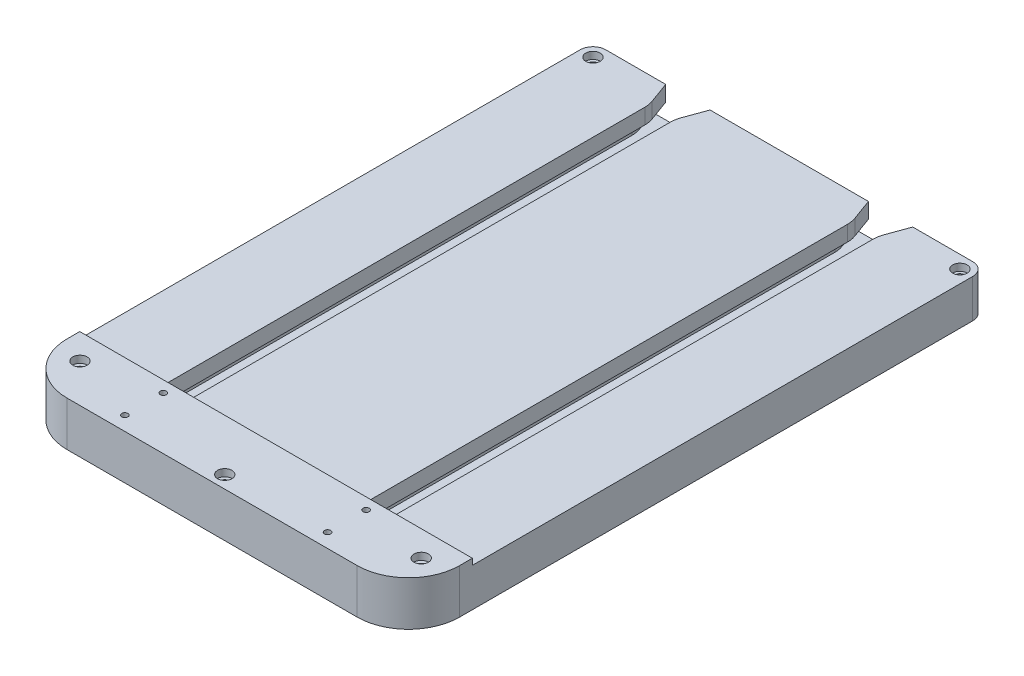
SolidWorks part; units mm, degrees
ref_plane "Front Plane" through (0, 0, 0) normal (0, 0, 1) x (1, 0, 0)
ref_plane "Top Plane" through (0, 0, 0) normal (0, 1, 0) x (1, 0, 0)
ref_plane "Right Plane" through (0, 0, 0) normal (1, 0, 0) x (0, 0, -1)
sketch "Sketch1" plane through (0, 0, 0) normal (0, 0, 1) x (1, 0, 0)
  line L0 (8.5758, -1.4682) -> (8.5758, -16.2855) construction
  line L1 (-88.5792, 2.7645) -> (-47.9392, 2.7645)
  line L2 (-88.5792, 2.7645) -> (-88.5792, -16.2855)
  line L3 (-88.5792, -16.2855) -> (105.7308, -16.2855)
  line L4 (105.7308, 2.7645) -> (105.7308, -16.2855)
  line L7 (-35.2392, 2.7645) -> (-35.2392, -4.8555)
  line L9 (-47.9392, 2.7645) -> (-47.9392, -4.8555)
  line L10 (-54.2892, -4.8555) -> (-47.9392, -4.8555)
  line L11 (-54.2892, -4.8555) -> (-54.2892, -12.4755)
  line L12 (-54.2892, -12.4755) -> (-28.8892, -12.4755)
  line L13 (-28.8892, -4.8555) -> (-28.8892, -12.4755)
  line L14 (65.0908, 2.7645) -> (65.0908, -4.8555)
  line L16 (52.3908, 2.7645) -> (52.3908, -4.8555)
  line L17 (71.4408, -12.4755) -> (46.0408, -12.4755)
  line L18 (46.0408, -4.8555) -> (46.0408, -12.4755)
  line L19 (71.4408, -4.8555) -> (65.0908, -4.8555)
  line L20 (71.4408, -4.8555) -> (71.4408, -12.4755)
  line L21 (-35.2392, -4.8555) -> (-28.8892, -4.8555)
  line L22 (-35.2392, 2.7645) -> (5.4008, 2.7645)
  line L23 (52.3908, -4.8555) -> (46.0408, -4.8555)
  line L24 (65.0908, 2.7645) -> (105.7308, 2.7645)
  line L25 (11.7508, 2.7645) -> (52.3908, 2.7645)
  line L27 (5.4008, 2.7645) -> (5.4008, 28.1645)
  line L28 (5.4008, 28.1645) -> (11.7508, 28.1645)
  line L29 (11.7508, 2.7645) -> (11.7508, 28.1645)
  dimension "D1" = 19.05
  dimension "D2" = 7.62
  dimension "D3" = 25.4
  dimension "D4" = 7.62
  dimension "D5" = 12.7
  dimension "D6" = 43.815
  dimension "D7" = 40.64
  dimension "D8" = 25.4
  dimension "D9" = 6.35
extrude "Boss-Extrude1" add sketch "Sketch1" along normal blind 254
sketch "Sketch2" plane through (0, 0, 254) normal (0, 0, 1) x (1, 0, 0)
  line L0 (105.7308, -16.2855) -> (105.7308, 2.7645) construction
  line L1 (-88.5792, -16.2855) -> (105.7308, -16.2855)
  line L2 (-88.5792, -16.2855) -> (-88.5792, 28.1645)
  line L3 (-88.5792, 28.1645) -> (105.7308, 28.1645)
  line L4 (105.7308, -16.2855) -> (105.7308, 28.1645)
  line L5 (11.7508, 28.1645) -> (5.4008, 28.1645) construction
  line L6 (105.7308, -16.2855) -> (105.7308, 2.7645)
  line L7 (11.7508, 28.1645) -> (5.4008, 28.1645)
  line L8 (5.4008, 2.7645) -> (-35.2392, 2.7645) construction
  line L9 (-35.2392, 2.7645) -> (-35.2392, -4.8555) construction
  line L10 (-47.9392, -4.8555) -> (-47.9392, 2.7645) construction
  line L11 (-47.9392, 2.7645) -> (-88.5792, 2.7645) construction
  line L12 (5.4008, 2.7645) -> (-35.2392, 2.7645)
  line L13 (-35.2392, 2.7645) -> (-35.2392, -4.8555)
  line L14 (-47.9392, -4.8555) -> (-47.9392, 2.7645)
  line L15 (-47.9392, 2.7645) -> (-88.5792, 2.7645)
  line L16 (8.5758, 28.1645) -> (8.5758, -16.2855) construction
  line L17 (-47.9392, 2.7645) -> (-35.2392, 2.7645)
  line L22 (-41.5892, 2.7645) -> (-41.5892, 5.8125)
  line L23 (-59.3692, 22.8305) -> (-23.8092, 22.8305)
  line L24 (-59.3692, 22.8305) -> (-59.3692, 5.8125)
  line L25 (-59.3692, 5.8125) -> (-23.8092, 5.8125)
  line L26 (-23.8092, 22.8305) -> (-23.8092, 5.8125)
  line L27 (76.5208, 5.8125) -> (40.9608, 5.8125)
  line L28 (40.9608, 22.8305) -> (40.9608, 5.8125)
  line L29 (76.5208, 22.8305) -> (40.9608, 22.8305)
  line L30 (76.5208, 22.8305) -> (76.5208, 5.8125)
  dimension "D1" = 17.018
  dimension "D2" = 35.56
  dimension "D3" = 3.048
  dimension "D4" = 90
extrude "Boss-Extrude2" add sketch "Sketch2" along normal blind 6.35
sketch "Sketch3" plane through (0, 0, 260.35) normal (0, 0, 1) x (1, 0, 0)
  line L0 (105.7308, -16.2855) -> (105.7308, 28.1645) construction
  line L1 (-88.5792, -16.2855) -> (105.7308, -16.2855)
  line L2 (-88.5792, -16.2855) -> (-88.5792, 5.8125)
  line L3 (-88.5792, 5.8125) -> (105.7308, 5.8125)
  line L4 (105.7308, -16.2855) -> (105.7308, 5.8125)
  line L5 (76.5208, 5.8125) -> (40.9608, 5.8125) construction
  line L6 (105.7308, -16.2855) -> (105.7308, 28.1645)
  line L7 (76.5208, 5.8125) -> (40.9608, 5.8125)
  line M8 (-88.5792, 28.1645) -> (-88.5792, -16.2855)
  line M9 (-88.5792, -16.2855) -> (105.7308, -16.2855)
  line M10 (105.7308, -16.2855) -> (105.7308, 28.1645)
  line M13 (76.5208, 5.8125) -> (40.9608, 5.8125)
  line M15 (-23.8092, 5.8125) -> (-59.3692, 5.8125)
extrude "Boss-Extrude3" add sketch "Sketch3" along normal blind 44.45 contours L3 M8 M9 M10 M13 M15
ref_plane "Plane1" through (-54.2892, -12.4755, 254) normal (-1, 0, 0) x (0, 0, 1)
sketch "Sketch5" plane through (0, 5.8125, 0) normal (0, 1, 0) x (1, 0, 0)
  line L0 (-41.5892, -254) -> (-41.5892, -329.45) construction
  line L1 (-59.3692, -254) -> (-23.8092, -254) construction
  line L2 (8.5758, -260.35) -> (8.5758, -328.2895) construction
  line L3 (-23.8092, -260.35) -> (40.9608, -260.35) construction
  circle A0 centre (-41.5892, -259.614) radius 1.524
  circle A1 centre (-41.5892, -278.664) radius 1.524
  circle A2 centre (58.7408, -259.614) radius 1.524
  circle A3 centre (58.7408, -278.664) radius 1.524
  dimension "D1" = 3.048
  dimension "D2" = 3.048
  dimension "D3" = 5.614
  dimension "D4" = 19.05
extrude "Cut-Extrude1" cut sketch "Sketch5" against normal through all and the other way through all contours A0 | A1 | A3 | A2
fillet "Fillet1" radius 3.175 3 edges at (8.5758, 28.1645, 0) (5.4008, 28.1645, 127) (11.7508, 28.1645, 127)
fillet "Fillet2" radius 3.175 8 edges at (8.5758, 28.1645, 260.35) (82.9031, 28.1645, 260.35) (58.7408, 28.1645, 258.09) (-41.5892, 28.1645, 258.09) (6.3308, 27.2346, 254) (-40.0017, 28.1645, 254) (-65.7514, 28.1645, 260.35) (-88.5792, 28.1645, 257.175)
hole_wizard "CBORE for #6 Socket Head Cap Screw1" positions "Sketch6" profile "Sketch7" counterbore size "#6" standard "ANSI Inch" end condition through all
sketch "Sketch6" plane through (0, 2.7645, 0) normal (0, 1, 0) x (1, 0, 0)
  line L0 (105.7308, 0) -> (65.0908, 0) construction
  line L1 (105.7308, -254) -> (105.7308, 0) construction
  line L2 (-88.5792, -254) -> (-88.5792, 0) construction
  line L3 (-47.9392, 0) -> (-88.5792, 0) construction
  point P0 (99.3808, -6.35)
  point P2 (-82.2292, -6.35)
  dimension "D1" = 6.35
  dimension "D2" = 6.35
  dimension "D3" = 6.35
  dimension "D4" = 6.35
sketch "Sketch7" plane through (99.3808, 2.7645, 6.35) normal (1, 0, 0) x (0, 0, 1)
  line L0 (0, 0) -> (0, 19.05)
  line L1 (0, 19.05) -> (2.1527, 19.05)
  line L3 (2.1527, 19.05) -> (2.1526, 3.5052)
  line L4 (2.1526, 3.5052) -> (3.5725, 3.5052)
  line L5 (3.5725, 3.5052) -> (3.5725, 0)
  line L7 (3.5725, 0) -> (0, 0)
  line L11 (0, -6.35) -> (0, 107.95) construction
  dimension "Thru Hole Dia." = 4.3053
  dimension "Thru Hole Depth" = 19.05
  dimension "C'Bore Dia." = 7.145
  dimension "C'Bore Depth" = 3.5052
chamfer "Chamfer1" distance 12.7 angle 20 8 edges at (-28.8892, -8.6655, 0) (-35.2392, -1.0455, 0) (-47.9392, -1.0455, 0) (-54.2892, -8.6655, 0) (52.3908, -1.0455, 0) (46.0408, -8.6655, 0) (71.4408, -8.6655, 0) (65.0908, -1.0455, 0)
fillet "Fillet4" radius 12.7 8 edges at (65.0908, -1.0455, 12.7) (52.3908, -1.0455, 12.7) (46.0408, -8.6655, 12.7) (71.4408, -8.6655, 12.7) (-54.2892, -8.6655, 12.7) (-28.8892, -8.6655, 12.7) (-35.2392, -1.0455, 12.7) (-47.9392, -1.0455, 12.7)
fillet "Fillet6" radius 6.35 2 edges at (-88.5792, -6.7605, 0) (105.7308, -6.7605, 0)
fillet "Fillet7" radius 2.54 3 edges at (5.4008, 13.877, 0) (8.5758, 28.1645, 0) (11.7508, 13.877, 0)
sketch "Sketch8" plane through (105.7308, 0, 0) normal (1, 0, 0) x (0, 0, -1)
  line L1 (-254, 2.7645) -> (3.9998, 2.7645)
  line L2 (-254, 2.7645) -> (-254, 5.8125)
  line L3 (-234.4635, 41.9327) -> (3.9998, 41.9327)
  line L4 (3.9998, 2.7645) -> (3.9998, 41.9327)
  line L5 (-260.35, 5.8125) -> (-254, 5.8125)
  line L6 (-260.35, 5.8125) -> (-260.35, 51.3744)
  line L7 (-260.35, 51.3744) -> (-234.4635, 51.3744)
  line L8 (-234.4635, 41.9327) -> (-234.4635, 51.3744)
  dimension "D2" = 257.9998
  dimension "D3" = 45.5619
extrude "Cut-Extrude2" cut sketch "Sketch8" against normal through all
sketch "Sketch13" plane through (105.7308, 0, 0) normal (1, 0, 0) x (0, 0, -1)
  line L1 (-304.8, -16.2855) -> (-285.6568, -16.2855)
  line L2 (-304.8, -16.2855) -> (-304.8, 26.8072)
  line L3 (-304.8, 26.8072) -> (-285.6568, 26.8072)
  line L4 (-285.6568, -16.2855) -> (-285.6568, 26.8072)
  dimension "D1" = 43.0927
  dimension "D2" = 19.1432
extrude "Cut-Extrude3" cut sketch "Sketch13" against normal through all
fillet "Fillet8" radius 25.4 2 edges at (-88.5792, -5.2365, 285.6568) (105.7308, -5.2365, 285.6568)
sketch "Sketch14" plane through (0, 5.8125, 0) normal (0, 1, 0) x (1, 0, 0)
  line L0 (80.3308, -285.6568) -> (-63.1792, -285.6568) construction
  line L1 (-88.5792, -260.2568) -> (-88.5792, -254) construction
  line L2 (105.7308, -254) -> (105.7308, -6.35) construction
  circle A0 centre (93.0308, -266.6068) radius 3.175
  circle A1 centre (-75.8792, -266.6068) radius 3.175
  dimension "D1" = 6.35
  dimension "D2" = 19.05
  dimension "D3" = 12.7
  dimension "D4" = 19.05
  dimension "D5" = 12.7
hole_wizard "CBORE for #6 Socket Head Cap Screw3" positions "Sketch11" profile "Sketch12" counterbore size "#6" standard "ANSI Inch" end condition through all
sketch "Sketch11" plane through (0, 5.8125, 0) normal (0, 1, 0) x (1, 0, 0)
  line L0 (-88.5792, -260.2568) -> (-88.5792, -254) construction
  line L1 (52.3908, -254) -> (-35.2392, -254) construction
  point P0 (8.5758, -279.4)
  dimension "D1" = 97.155
  dimension "D2" = 25.4
sketch "Sketch12" plane through (8.5758, 5.8125, 279.4) normal (1, 0, 0) x (0, 0, 1)
  line L0 (0, 0) -> (0, 22.098)
  line L1 (0, 22.098) -> (1.8288, 22.098)
  line L3 (1.8288, 22.098) -> (1.8288, 3.5052)
  line L4 (1.8288, 3.5052) -> (3.5725, 3.5052)
  line L5 (3.5725, 3.5052) -> (3.5725, 0)
  line L7 (3.5725, 0) -> (0, 0)
  line L11 (0, -6.35) -> (0, 107.95) construction
  dimension "Thru Hole Dia." = 3.6576
  dimension "Thru Hole Depth" = 22.098
  dimension "C'Bore Dia." = 7.145
  dimension "C'Bore Depth" = 3.5052
hole_wizard "CBORE for #6 Socket Head Cap Screw4" positions "Sketch15" profile "Sketch16" counterbore size "#6" standard "ANSI Inch" end condition through all
sketch "Sketch15" plane through (0, 5.8125, 0) normal (0, 1, 0) x (1, 0, 0)
  point P0 (93.0308, -266.6068)
  point P3 (-75.8792, -266.6068)
sketch "Sketch16" plane through (93.0308, 5.8125, 266.6068) normal (1, 0, 0) x (0, 0, 1)
  line L0 (0, 0) -> (0, 22.098)
  line L1 (0, 22.098) -> (1.8288, 22.098)
  line L3 (1.8288, 22.098) -> (1.8288, 3.5052)
  line L4 (1.8288, 3.5052) -> (3.5725, 3.5052)
  line L5 (3.5725, 3.5052) -> (3.5725, 0)
  line L7 (3.5725, 0) -> (0, 0)
  line L11 (0, -6.35) -> (0, 107.95) construction
  dimension "Thru Hole Dia." = 3.6576
  dimension "Thru Hole Depth" = 22.098
  dimension "C'Bore Dia." = 7.145
  dimension "C'Bore Depth" = 3.5052
